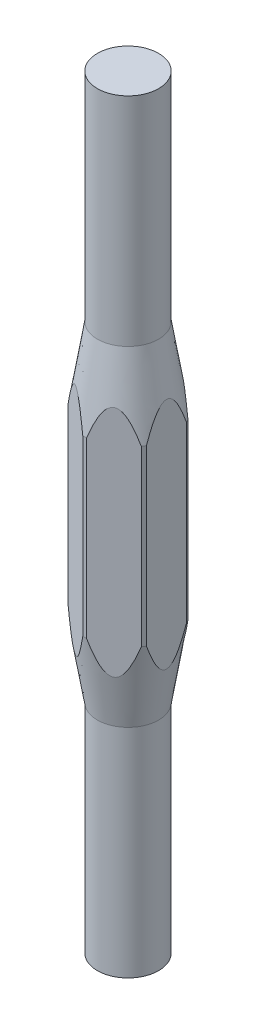
SolidWorks part; units mm, degrees
material "6061-T6 (SS)"
ref_plane "Front Plane" through (0, 0, 0) normal (0, 0, 1) x (1, 0, 0)
ref_plane "Top Plane" through (0, 0, 0) normal (0, 1, 0) x (1, 0, 0)
ref_plane "Right Plane" through (0, 0, 0) normal (1, 0, 0) x (0, 0, -1)
sketch "Sketch1" plane through (0, 0, 0) normal (0, 0, 1) x (1, 0, 0)
  line L0 (2.2371, -12.065) -> (3.175, -6.35)
  line L1 (3.175, -6.35) -> (3.175, 6.35)
  line L2 (3.175, 6.35) -> (2.2371, 12.065)
  line L3 (2.2371, 12.065) -> (2.2371, -12.065)
  line L4 (2.2371, 0) -> (3.175, 0) construction
  line L5 (0, 6.0414) -> (0, -4.6122) construction
  dimension "D1" = 24.13
  dimension "D2" = 12.7
  dimension "D3" = 3.175
revolve "Revolve1" add sketch "Sketch1" angle 360 about L5
ref_plane "Plane1" through (0, 0, 3.175) normal (0, 0, 1) x (1, 0, 0)
sketch "Sketch3" plane through (0, 0, 3.175) normal (0, 0, 1) x (1, 0, 0)
  line L1 (-3.2443, -10.1093) -> (-2.8155, -10.1093)
  line L2 (-3.2443, -10.1093) -> (-3.2443, 8.7912)
  line L3 (-3.2443, 8.7912) -> (-2.8155, 8.7912)
  line L4 (-2.8155, -10.1093) -> (-2.8155, 8.7912)
extrude "Cut-Extrude1" cut sketch "Sketch3" against normal through all
pattern_circular "CirPattern1" count 6 over 360 about axis through (0, 6.0414, 0) along (0, 1, 0) of "Cut-Extrude1"
sketch "Sketch5" plane through (0, 0, 0) normal (0, 1, 0) x (1, 0, 0)
  circle A0 centre (0, 0) radius 2.2371
  circle A1 centre (0, 0) radius 2.2371 construction
extrude "Boss-Extrude1" add sketch "Sketch5" along normal blind 27.94 and the other way blind 27.94
